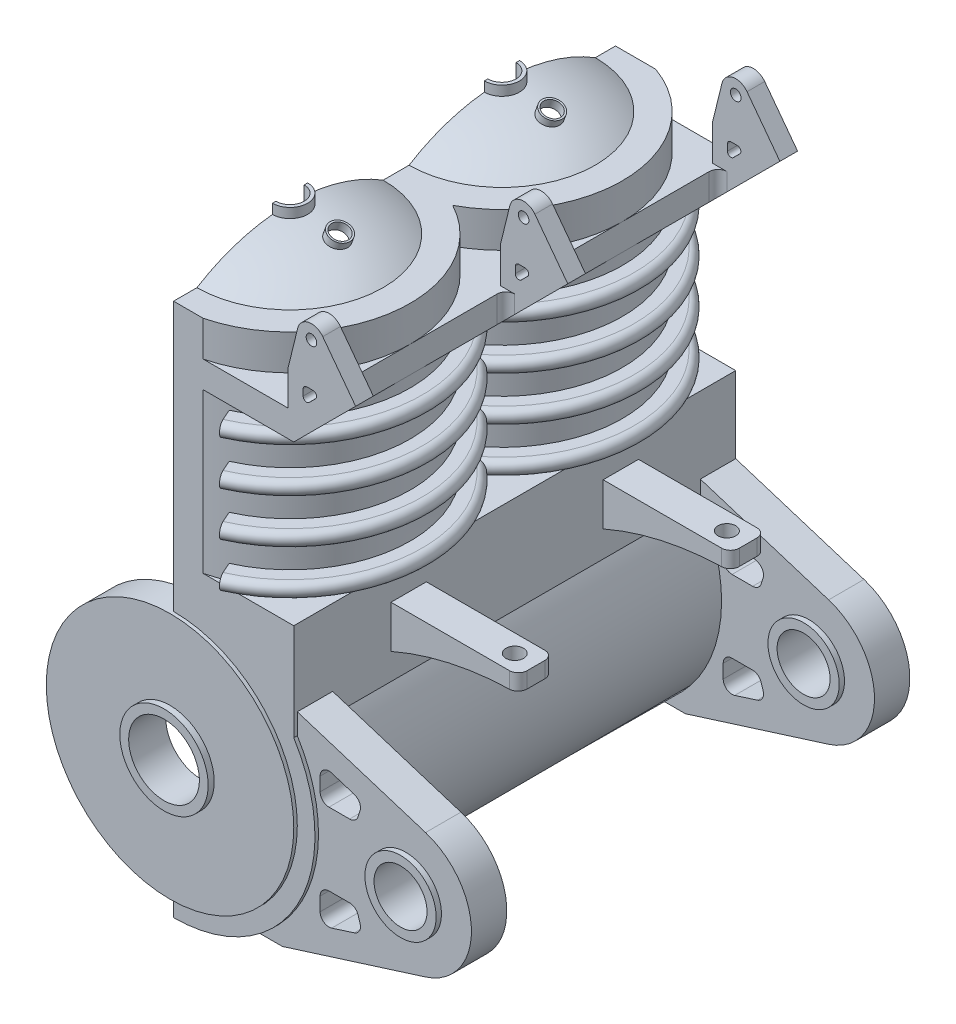
SolidWorks part; units mm, degrees
ref_plane "Front Plane" through (0, 0, 0) normal (0, 0, 1) x (1, 0, 0)
ref_plane "Top Plane" through (0, 0, 0) normal (0, 1, 0) x (1, 0, 0)
ref_plane "Right Plane" through (0, 0, 0) normal (1, 0, 0) x (0, 0, -1)
sketch "Sketch2" plane through (0, 0, 0) normal (0, 0, 1) x (1, 0, 0)
  line L0 (0, 28.2) -> (0, 0)
  line L1 (6.8, 12.2143) -> (6.8, 28.2)
  line L2 (0, 28.2) -> (6.8, 28.2)
  arc A0 (0, 0) -> (6.8, 12.2143) centre (0, 8) ccw
  dimension "D1" = 8
  dimension "D2" = 6.8
  dimension "D3" = 28.2
sketch "Sketch3" plane through (0, 0, 0) normal (0, 0, 1) x (1, 0, 0)
sketch "Sketch5" plane through (0, 0, 0) normal (0, 0, 1) x (1, 0, 0)
  line L0 (0, 28.2) -> (0, 0) construction
extrude "Boss-Extrude1" add sketch "Sketch2" along normal blind 25
sketch "Sketch7" plane through (0, 28.2, 0) normal (0, 1, 0) x (1, 0, 0)
  line L0 (0, -25) -> (0, 0) construction
  circle A0 centre (0, -6.41) radius 5
  circle A1 centre (0, -18.41) radius 5
  dimension "D2" = 10
  dimension "D1" = 12
  dimension "D3" = 6.59
extrude "Cut-Extrude1" cut sketch "Sketch7" against normal blind 20
sketch "Sketch8" plane through (0, 0, 25) normal (0, 0, 1) x (1, 0, 0)
  circle A0 centre (0, 8) radius 7
  dimension "D1" = 14
extrude "Cut-Extrude2" cut sketch "Sketch8" against normal through all
ref_plane "Ref-plane-cylinder shape" through (0, 26.7, 0) normal (0, 1, 0) x (1, 0, 0)
sketch "Sketch10" plane through (0, 26.7, 0) normal (0, 1, 0) x (1, 0, 0)
  line L0 (0, 0.39) -> (7.4574, 0.39)
  line L1 (7.4574, 0.39) -> (7.4574, -25.21)
  line L2 (7.4574, -25.21) -> (0, -25.21)
  arc A7 (0, -25.21) -> (0, -11.61) centre (0, -18.41) ccw
  arc A8 (0, -25.21) -> (3.2, -12.41) centre (0, -18.41) ccw
  arc A10 (0, -13.21) -> (0, 0.39) centre (0, -6.41) ccw
  arc A11 (3.2, -12.41) -> (0, 0.39) centre (0, -6.41) ccw
  dimension "D1" = 1.8
  dimension "D2" = 1.8
extrude "Cut-Extrude3" cut sketch "Sketch10" against normal blind 9
sketch "Sketch12" plane through (0, 0, 0) normal (-1, 0, 0) x (0, 0, 1)
  line L0 (1.41, 28.2) -> (0, 28.2) construction
  line L1 (0.68, 27.35) -> (0.175, 27.35)
  line L2 (0.68, 27.35) -> (0.68, 17.35)
  line L3 (0.68, 17.35) -> (0.175, 17.35)
  line L4 (0.175, 27.35) -> (0.175, 17.35)
  line L5 (0.68, 27.35) -> (0.175, 17.35) construction
  line L6 (0.68, 17.35) -> (0.175, 27.35) construction
  line L7 (0, 28.2) -> (0, 15) construction
  line L8 (-0.7062, 17.9838) -> (-1.07, 17.75) construction
  line L9 (0.175, 26.05) -> (-1.07, 26.05)
  line L10 (0.175, 26.05) -> (0.175, 25.25)
  line L11 (0.175, 25.25) -> (-1.07, 25.25)
  line L13 (0.175, 26.05) -> (-0.7062, 25.4838) construction
  line L14 (0.175, 25.25) -> (-0.7062, 25.8162) construction
  line L15 (0.175, 23.55) -> (-1.07, 23.55)
  line L16 (0.175, 23.55) -> (0.175, 22.75)
  line L17 (0.175, 22.75) -> (-1.07, 22.75)
  line L19 (0.175, 23.55) -> (-0.4475, 23.15) construction
  line L20 (0.175, 22.75) -> (-0.7062, 23.3162) construction
  line L21 (0.175, 21.05) -> (-1.07, 21.05)
  line L22 (0.175, 21.05) -> (0.175, 20.25)
  line L23 (0.175, 20.25) -> (-1.07, 20.25)
  line L25 (0.175, 21.05) -> (-0.4475, 20.65) construction
  line L26 (0.175, 20.25) -> (-0.7062, 20.8162) construction
  line L27 (0.175, 18.55) -> (-1.07, 18.55)
  line L28 (0.175, 18.55) -> (0.175, 17.75)
  line L29 (0.175, 17.75) -> (-1.07, 17.75)
  line L31 (0.175, 18.55) -> (-0.4475, 18.15) construction
  line L32 (0.175, 17.75) -> (-0.7062, 18.3162) construction
  line L33 (-0.7062, 20.4838) -> (-1.07, 20.25) construction
  line L35 (6.41, 28.2) -> (6.41, 30.9302) construction
  line L36 (11.41, 28.2) -> (1.41, 28.2) construction
  arc A0 (-1.07, 26.05) -> (-1.07, 25.25) centre (-1.07, 25.65) ccw
  arc A1 (-1.07, 23.55) -> (-1.07, 22.75) centre (-1.07, 23.15) ccw
  arc A2 (-1.07, 21.05) -> (-1.07, 20.25) centre (-1.07, 20.65) ccw
  arc A3 (-1.07, 18.55) -> (-1.07, 17.75) centre (-1.07, 18.15) ccw
  point P4 (0.4275, 22.35)
  point P13 (-0.4475, 25.65)
  point P18 (-0.4475, 23.15)
  point P23 (-0.4475, 20.65)
  point P28 (-0.4475, 18.15)
  dimension "D1" = 10
  dimension "D2" = 0.505
  dimension "D3" = 0.85
  dimension "D4" = 0.68
  dimension "D6" = 0.8
  dimension "D7" = 2.15
  dimension "D8" = 2.5
  dimension "D9" = 2.5
  dimension "D10" = 2.5
revolve "Revolve1" add sketch "Sketch12" angle 156 about L35 region at (0, 22.35, 0.4275) region at (0, 25.65, 0.0875) region at (0, 25.65, -0.695) region at (0, 18.15, 0.0875) region at (0, 23.15, 0.0875) region at (0, 18.15, -0.695) region at (0, 23.15, -0.695) region at (0, 20.65, 0.0875) region at (0, 20.65, -0.695) reverse direction yes
pattern_linear "LPattern1" count 2 spacing 12 along (0, 0, 1) of "Revolve1"
sketch "Sketch13" plane through (0, 28.2, 0) normal (0, 1, 0) x (1, 0, 0)
  circle A0 centre (0, -6.41) radius 5.0386
extrude "Cut-Extrude4" cut sketch "Sketch13" against normal blind 15
sketch "Sketch14" plane through (0, 0, 0) normal (0, 0, -1) x (-1, 0, 0)
  circle A1 centre (0, 8) radius 7
  circle A2 centre (0, 8) radius 2.5
  dimension "D1" = 5
  dimension "D2" = 14
extrude "Boss-Extrude2" add sketch "Sketch14" along normal blind 0.5 and the other way blind 1
pattern_linear "LPattern3" count 3 spacing 12 along (0, 0, 1) of "Boss-Extrude2"
sketch "Sketch15" plane through (0, 0, 25) normal (0, 0, 1) x (1, 0, 0)
  circle A0 centre (0, 8) radius 7
extrude "Boss-Extrude4" add sketch "Sketch15" along normal blind 0.2
sketch "Sketch16" plane through (0, 0, -0.5) normal (0, 0, -1) x (-1, 0, 0)
  circle A0 centre (0, 8) radius 2.5 construction
  circle A1 centre (0, 8) radius 2.5
  circle A2 centre (0, 8) radius 2
  dimension "D1" = 4
extrude "Boss-Extrude5" add sketch "Sketch16" along normal blind 0.5 and the other way blind 1.6
pattern_linear "LPattern4" count 3 spacing 12.22 along (0, 0, 1) of "Boss-Extrude5"
sketch "Sketch18" plane through (0, 28.2, 0) normal (0, 1, 0) x (1, 0, 0)
  line L0 (0, -13.41) -> (0, -11.4486) construction
  line L1 (0, -13.41) -> (0, -11.4486)
  line L2 (0, -23.41) -> (0, -25)
  line L3 (2, -25) -> (-2, -25) construction
  line L4 (0, -25) -> (1.6769, -25)
  line L5 (2.2698, 0) -> (0, 0)
  line L6 (0, 0) -> (0, -1.3714)
  arc A0 (6.8, -6.41) -> (2.2698, 0) centre (0, -6.41) ccw construction
  arc A1 (3.2, -12.41) -> (6.8, -6.41) centre (0, -6.41) ccw construction
  arc A2 (0, -23.41) -> (0, -13.41) centre (0, -18.41) ccw construction
  arc A3 (0, -11.4486) -> (0, -1.3714) centre (0, -6.41) ccw construction
  arc A4 (6.8, -6.41) -> (2.2698, 0) centre (0, -6.41) ccw
  arc A5 (3.2, -12.41) -> (6.8, -6.41) centre (0, -6.41) ccw
  arc A6 (0, -23.41) -> (0, -13.41) centre (0, -18.41) ccw
  arc A7 (0, -11.4486) -> (0, -1.3714) centre (0, -6.41) ccw
  arc A8 (1.6769, -25) -> (6.8, -18.41) centre (0, -18.41) ccw construction
  arc A9 (6.8, -18.41) -> (3.2, -12.41) centre (0, -18.41) ccw construction
  arc A10 (1.6769, -25) -> (6.8, -18.41) centre (0, -18.41) ccw
  arc A11 (6.8, -18.41) -> (3.2, -12.41) centre (0, -18.41) ccw
extrude "Boss-Extrude6" add sketch "Sketch18" along normal blind 2 contours L6 A7 L1 A6 L2 L4 A10 A11 A5 A4 L5
sketch "Sketch22" plane through (0, 0, 25.2) normal (0, 0, 1) x (1, 0, 0)
  circle A0 centre (0, 8) radius 2
extrude "Cut-Extrude5" cut sketch "Sketch22" against normal through all
sketch "Sketch23" plane through (0, 0, 0) normal (0, 0, -1) x (-1, 0, 0)
  line L0 (0, 8) -> (-23.8537, 8) construction
  line L1 (-8.3219, 7.5575) -> (-12.94, 7.5575) construction
  line L2 (-6.8, 13.3835) -> (-14.0556, 11.0958)
  line L3 (-6.8, 12.2143) -> (-6.8, 17.7) construction
  line L4 (-14.0556, 4.0192) -> (-5.9539, 1.4648)
  line L5 (-5.9539, 1.4648) -> (-4.6142, 1.4648)
  circle A0 centre (-12.94, 7.5575) radius 2.015
  arc A1 (-14.0556, 11.0958) -> (-14.0556, 4.0192) centre (-12.94, 7.5575) ccw
  arc A2 (-6.8, 12.2143) -> (0, 0) centre (0, 8) ccw construction
  line M10 (-6.8, 17.7) -> (-6.8, 12.2143)
  arc M11 (-6.8, 12.2143) -> (0, 0) centre (0, 8) ccw
  dimension "D3" = 4.03
  dimension "D4" = 3.71
  dimension "D1" = 0.4425
  dimension "D2" = 12.94
  dimension "D5" = 35
  dimension "D6" = 1.3398
extrude "Boss-Extrude7" add sketch "Sketch23" against normal blind 2 contours L2 A1 L4 L5 A0 M11 M10 region at (10.8001, 7.3361, 0)
pattern_linear "LPattern5" count 2 spacing 22.8 along (0, 0, 1) of "Boss-Extrude7"
sketch "Sketch25" plane through (0, 0, 0) normal (0, 0, -1) x (-1, 0, 0)
  circle A0 centre (-12.94, 7.5575) radius 2.015 construction
  circle A1 centre (-12.94, 7.5575) radius 2.015
  circle A2 centre (-12.94, 7.5575) radius 1.5
  dimension "D1" = 3
extrude "Boss-Extrude8" add sketch "Sketch25" along normal blind 0.3 and the other way blind 2.3
pattern_linear "LPattern6" count 2 spacing 22.8 along (0, 0, 1) of "Boss-Extrude8"
sketch "Sketch26" plane through (0, 0, 0) normal (0, 0, -1) x (-1, 0, 0)
  line L0 (-8.7441, 11.357) -> (-10.0262, 10.9477)
  line L1 (-10.3504, 10.3194) -> (-10.2352, 9.9584)
  line L2 (-9.7589, 9.6105) -> (-8.592, 9.6105)
  line L3 (-8.092, 10.1105) -> (-8.092, 10.8807)
  line L4 (-12.94, 7.5575) -> (-7.2364, 7.5575) construction
  line L5 (-8.092, 5.0045) -> (-8.092, 4.2343)
  line L6 (-9.7589, 5.5045) -> (-8.592, 5.5045)
  line L7 (-10.3504, 4.7956) -> (-10.2352, 5.1566)
  line L8 (-8.7441, 3.758) -> (-10.0262, 4.1673)
  arc A0 (-10.0262, 10.9477) -> (-10.3504, 10.3194) centre (-9.8741, 10.4714) ccw
  arc A1 (-10.2352, 9.9584) -> (-9.7589, 9.6105) centre (-9.7589, 10.1105) ccw
  arc A2 (-8.592, 9.6105) -> (-8.092, 10.1105) centre (-8.592, 10.1105) ccw
  arc A3 (-8.7441, 11.357) -> (-8.092, 10.8807) centre (-8.592, 10.8807) cw
  arc A4 (-8.7441, 3.758) -> (-8.092, 4.2343) centre (-8.592, 4.2343) ccw
  arc A5 (-8.592, 5.5045) -> (-8.092, 5.0045) centre (-8.592, 5.0045) cw
  arc A6 (-10.2352, 5.1566) -> (-9.7589, 5.5045) centre (-9.7589, 5.0045) cw
  arc A7 (-10.0262, 4.1673) -> (-10.3504, 4.7956) centre (-9.8741, 4.6436) cw
  dimension "D1" = 0.5
extrude "Cut-Extrude6" cut sketch "Sketch26" against normal through all
sketch "Sketch27" plane through (0, 0, 0) normal (-1, 0, 0) x (0, 0, 1)
  line L0 (18.41, 30.2) -> (18.41, 21.7) construction
  line L1 (23.41, 30.2) -> (13.41, 30.2) construction
  line L2 (13.41, 30.2) -> (11.4486, 30.2) construction
  line L3 (18.41, 22.821) -> (18.41, 31.3079) construction
  line L4 (18.41, 31.7) -> (18.41, 31.58)
  line L5 (13.1422, 30.2) -> (13.3737, 30.2)
  line L6 (13.3737, 30.2) -> (23.41, 30.2)
  line L7 (13.3737, 30.2) -> (23.41, 30.2)
  arc A0 (13.1422, 30.2) -> (18.41, 31.7) centre (18.41, 21.7) cw
  arc A1 (13.3737, 30.2) -> (18.41, 31.58) centre (18.41, 21.7) cw
  arc A2 (13.2054, 30.098) -> (18.41, 31.58) centre (18.41, 21.7) cw construction
  dimension "D1" = 10
  dimension "D3" = 0.12
  dimension "D2" = 8.5
revolve "Revolve3" add sketch "Sketch27" angle 180 about L0
pattern_linear "LPattern7" count 2 spacing 12 along (0, 0, -1) of "Revolve3"
sketch "Sketch32" plane through (0, 30.2, 0) normal (0, 1, 0) x (1, 0, 0)
  line L0 (0, -13.1422) -> (0, -23.6778) construction
  circle A0 centre (0, -6.4238) radius 0.995
  circle A1 centre (0, -18.41) radius 0.995
  dimension "D1" = 1.99
  dimension "D2" = 1.99
extrude "Cut-Extrude7" cut sketch "Sketch32" along normal blind 10.3
sketch "Sketch33" plane through (0, 30.2, 0) normal (0, 1, 0) x (1, 0, 0)
  line L0 (0, -17.415) -> (0, -17.61)
  line L1 (0, -19.21) -> (0, -19.405)
  line L2 (0, -5.4288) -> (0, -5.6238)
  line L3 (0, -7.2238) -> (0, -7.4188)
  arc A0 (0, -7.4188) -> (0, -5.4288) centre (0, -6.4238) ccw construction
  arc A1 (0, -7.4188) -> (0, -5.4288) centre (0, -6.4238) ccw
  arc A2 (0, -19.405) -> (0, -17.415) centre (0, -18.41) ccw construction
  arc A3 (0, -19.405) -> (0, -17.415) centre (0, -18.41) ccw
  arc A4 (0, -19.21) -> (0, -17.61) centre (0, -18.41) ccw
  arc A5 (0, -7.2238) -> (0, -5.6238) centre (0, -6.4238) ccw
  dimension "D1" = 0.8
  dimension "D2" = 0.8
extrude "Boss-Extrude9" add sketch "Sketch33" along normal blind 0.8 from offset 1.2
ref_plane "Plane3" through (9.7061, 26.6673, 0) normal (0.342, 0.9397, 0) x (0, 0, 1)
sketch "Sketch35" plane through (9.7061, 26.6673, 0) normal (0.342, 0.9397, 0) x (0, 0, 1)
  line L0 (6.41, -8.0546) -> (6.41, -8.636) construction
  line L1 (6.41, -7.6756) -> (6.41, -10.9673) construction
  line L2 (18.41, -5.874) -> (18.41, -10.1813) construction
  line L3 (6.41, -11.194) -> (6.41, -8.194) construction
  line L4 (6.41, -8.194) -> (7.01, -8.194) construction
  line L5 (18.41, -8.194) -> (18.41, -11.013) construction
  line L7 (17.81, -8.194) -> (18.41, -8.194) construction
  circle A0 centre (6.41, -8.194) radius 0.6
  circle A1 centre (18.41, -8.194) radius 0.6
  dimension "D1" = 1.2
  dimension "D2" = 1.2
  dimension "D3" = 3
  dimension "D4" = 2.819
extrude "Cut-Extrude8" cut sketch "Sketch35" along normal blind 10.8
sketch "Sketch36" plane through (0, 0, 0) normal (0, 0, -1) x (-1, 0, 0)
  line L0 (-6.8, 26.7) -> (-6.485, 26.7)
  line L1 (-6.8, 26.7) -> (-2.2698, 26.7) construction
  line L2 (-6.485, 26.7) -> (-6.485, 30.2)
  line L3 (-2.2698, 30.2) -> (-6.8, 30.2) construction
  line L4 (-6.485, 30.2) -> (-8.8, 30.2)
  line L5 (-8.8, 30.2) -> (-9.9243, 31.3243)
  line L7 (-10.6743, 30.5743) -> (-6.8, 26.7)
  line L8 (-8.0308, 29.4308) -> (-7.6711, 29.0711)
  line L9 (-7.3296, 29.2125) -> (-7.3296, 29.5722)
  line L10 (-7.5296, 29.7722) -> (-7.8894, 29.7722)
  arc A1 (-9.9243, 31.3243) -> (-10.6556, 30.5556) centre (-10.2995, 30.9491) ccw
  circle A2 centre (-10.2995, 30.9491) radius 0.3
  arc A3 (-7.6711, 29.0711) -> (-7.3296, 29.2125) centre (-7.5296, 29.2125) ccw
  arc A4 (-8.0308, 29.4308) -> (-7.8894, 29.7722) centre (-7.8894, 29.5722) cw
  arc A5 (-7.3296, 29.5722) -> (-7.5296, 29.7722) centre (-7.5296, 29.5722) ccw
  line M16 (-2.2698, 28.2) -> (-6.8, 28.2)
  line M17 (-6.8, 28.2) -> (-6.8, 26.7)
  dimension "D5" = 0.6
  dimension "D6" = 0.2
  dimension "D1" = 135
  dimension "D2" = 0.315
  dimension "D3" = 2.315
  dimension "D4" = 1.59
extrude "Boss-Extrude10" add sketch "Sketch36" against normal blind 1 contours L5 A1 L7 L2 L4 A5 L9 A3 L8 A4 L10 A2 M17 M16 region at (8.2085, 29.3056, 0)
pattern_linear "LPattern8" count 3 spacing 12 along (0, 0, 1) of "Boss-Extrude10"
fillet "Fillet2" radius 0.5 4 edges at (6.8, 27.45, 1) (6.8, 27.45, 24) (6.8, 27.45, 13) (6.8, 27.45, 12)
sketch "Sketch37" plane through (0, 0, 0) normal (0, 0, -1) x (-1, 0, 0)
  line L0 (-6.8, 16.1) -> (-14, 16.1)
  line L1 (-6.8, 13.3835) -> (-6.8, 17.7) construction
  line L2 (-14, 16.1) -> (-14, 15.2)
  line L3 (-6.8, 17.7) -> (-6.8, 16.1)
  line L4 (-6.8, 13.6927) -> (-6.8, 16.1)
  line L12 (-6.8, 17.7) -> (-6.8, 13.3835)
  line L13 (-6.8, 13.3835) -> (-14.0556, 11.0958)
  line L14 (-14.0556, 4.0192) -> (-5.9539, 1.4648)
  line L15 (-5.9539, 1.4648) -> (-4.6142, 1.4648)
  line L16 (0, 0) -> (0, 1)
  line L17 (0, 15) -> (0, 17.75)
  line L18 (0, 17.75) -> (-2.2698, 17.75)
  line L19 (-2.2698, 17.75) -> (-2.2698, 17.7)
  line L20 (-2.2698, 17.7) -> (-6.8, 17.7)
  line L21 (-6.8, 13.6927) -> (-6.8, 13.3835)
  line L22 (-6.8, 13.3835) -> (-14.0556, 11.0958)
  line L23 (-14.0556, 4.0192) -> (-5.9539, 1.4648)
  line L24 (-5.9539, 1.4648) -> (-4.6142, 1.4648)
  line L25 (0, 0) -> (0, 1)
  line L26 (0, 15) -> (0, 17.75)
  line L27 (0, 17.75) -> (-2.2698, 17.75)
  line L28 (-2.2698, 17.75) -> (-2.2698, 17.7)
  line L29 (-2.2698, 17.7) -> (-6.8, 17.7)
  arc A0 (-14, 15.2) -> (-6.8, 13.6927) centre (-14, -2.75) cw
  circle A1 centre (0, 8) radius 2.5 construction
  arc A5 (-14.0556, 11.0958) -> (-14.0556, 4.0192) centre (-12.94, 7.5575) ccw
  arc A6 (-4.6142, 1.4648) -> (0, 0) centre (0, 8) ccw
  arc A7 (0, 15) -> (0, 1) centre (0, 8) ccw
  arc A8 (-14.0556, 11.0958) -> (-14.0556, 4.0192) centre (-12.94, 7.5575) ccw
  arc A9 (-4.6142, 1.4648) -> (0, 0) centre (0, 8) ccw
  arc A10 (0, 15) -> (0, 1) centre (0, 8) ccw
  line M33 (-6.8, 17.7) -> (-6.8, 13.3835)
  dimension "D3" = 17.95
  dimension "D1" = 7.2
  dimension "D2" = 0.9
  dimension "D4" = 8.1
  dimension "D5" = 0
extrude "Boss-Extrude11" add sketch "Sketch37" against normal blind 2 from offset 5.5 contours L2 A0 L0 M33 region at (9.7569, 15.3316, 0) offset against normal yes
pattern_linear "LPattern9" count 2 spacing 12 along (0, 0, 1) of "Boss-Extrude11"
sketch "Sketch38" plane through (0, 16.1, 0) normal (0, 1, 0) x (1, 0, 0)
  line L0 (12.8, -6.5) -> (14, -6.5) construction
  line L1 (14, -7.5) -> (14, -5.5) construction
  line L2 (14, -19.5) -> (14, -17.5) construction
  line L3 (12.8, -18.5) -> (14, -18.5) construction
  circle A0 centre (12.8, -6.5) radius 0.5
  circle A1 centre (12.8, -18.5) radius 0.5
  dimension "D2" = 1
  dimension "D4" = 1
  dimension "D1" = 1.2
  dimension "D3" = 1.2
extrude "Cut-Extrude9" cut sketch "Sketch38" against normal blind 2
fillet "Fillet4" radius 0.5 4 edges at (14, 15.65, 5.5) (14, 15.65, 7.5) (14, 15.65, 17.5) (14, 15.65, 19.5)
sketch "Sketch39" plane through (0, 0, 0) normal (0, 0, -1) x (-1, 0, 0)
  line L0 (-6.485, 30.2) -> (-8.8, 30.2) construction
  line L1 (-13.2801, 33.0381) -> (-7.2847, 33.0381)
  line L2 (-13.2801, 33.0381) -> (-13.2801, 30.2)
  line L3 (-13.2801, 30.2) -> (-7.2847, 30.2)
  line L4 (-7.2847, 33.0381) -> (-7.2847, 30.2)
  line L5 (-13.2801, 33.0381) -> (-7.2847, 30.2) construction
  line L6 (-13.2801, 30.2) -> (-7.2847, 33.0381) construction
  point P4 (-10.2824, 31.619)
extrude "Cut-Extrude10" cut sketch "Sketch39" against normal through all
sketch "Sketch40" plane through (0, 0, 0) normal (0, 0, -1) x (-1, 0, 0)
  line L0 (-6.485, 30.2) -> (-7.0231, 32.3908)
  line L1 (-8.44, 32.68) -> (-10.3, 30.2)
  line L2 (0, 32.2) -> (0, 31.6517) construction
  line L3 (-6.485, 30.2) -> (-10.3, 30.2) construction
  circle A0 centre (-7.8, 32.2) radius 0.3
  arc A1 (-7.0231, 32.3908) -> (-8.44, 32.68) centre (-7.8, 32.2) ccw
  line M2 (-6.485, 30.2) -> (-10.3, 30.2)
  dimension "D1" = 7.8
  dimension "D2" = 2
  dimension "D3" = 0.8
  dimension "D4" = 0.6
extrude "Boss-Extrude12" add sketch "Sketch40" against normal blind 1 contours L0 A1 L1 A0 M2 region at (8.1305, 31.2688, 0)
pattern_linear "LPattern10" count 3 spacing 12 along (0, 0, 1) of "Boss-Extrude12"
extrude "Extrude-Thin1" add sketch "Sketch35<2>" along normal blind 0.5 from offset 1.9 thin thin type one direction reverse wall 0.1
sketch "Sketch35<2>" plane through (9.7061, 26.6673, 0) normal (0.342, 0.9397, 0) x (0, 0, 1) same geometry as "Sketch35"
